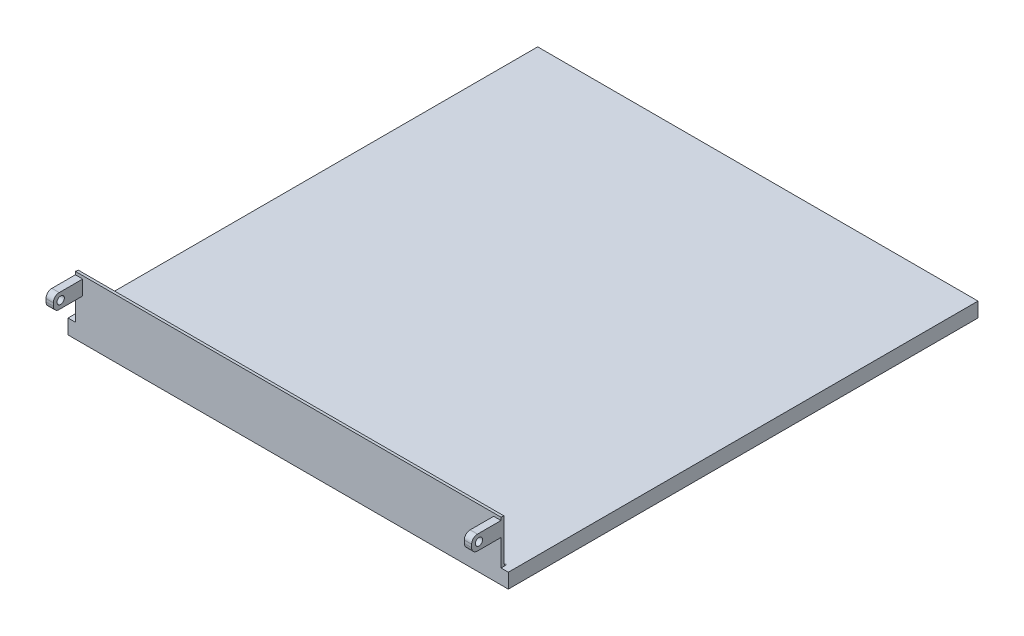
SolidWorks part; units mm, degrees
material "POLYURETHANE (11671)"
ref_plane "Front Plane" through (0, 0, 0) normal (0, 0, 1) x (1, 0, 0)
ref_plane "Top Plane" through (0, 0, 0) normal (0, 1, 0) x (1, 0, 0)
ref_plane "Right Plane" through (0, 0, 0) normal (1, 0, 0) x (0, 0, -1)
sketch "Sketch1" plane through (0, 0, 0) normal (0, 1, 0) x (1, 0, 0)
  line L1 (190.5, -203.2) -> (-190.5, -203.2)
  line L2 (190.5, -203.2) -> (190.5, 203.2)
  line L3 (190.5, 203.2) -> (-190.5, 203.2)
  line L4 (-190.5, -203.2) -> (-190.5, 203.2)
  line L5 (190.5, -203.2) -> (-190.5, 203.2) construction
  line L6 (190.5, 203.2) -> (-190.5, -203.2) construction
  point P0 (0, 0)
  dimension "D1" = 381
  dimension "D2" = 406.4
extrude "Boss-Extrude1" add sketch "Sketch1" against normal blind 12.7
sketch "Sketch2" plane through (0, -12.7, 0) normal (0, -1, 0) x (-1, 0, 0)
  line L0 (0, -203.2) -> (0, 203.2)
  line L1 (190.5, -203.2) -> (-190.5, -203.2) construction
  line L2 (-190.5, 203.2) -> (190.5, 203.2) construction
sketch "Sketch3" plane through (0, 0, 0) normal (1, 0, 0) x (0, 0, -1)
  line L0 (203.2, 0) -> (-203.2, 0)
sketch "Sketch5" plane through (0, 0, -203.2) normal (0, 0, -1) x (-1, 0, 0)
  line L0 (-190.5, 0) -> (0, -12.7)
  line L1 (-190.5, -12.7) -> (190.5, -12.7) construction
  line L2 (0, -12.7) -> (-190.5, -12.7)
  line L3 (-190.5, -12.7) -> (-190.5, 0)
  line L4 (0, -12.7) -> (190.5, -12.7)
  line L5 (190.5, -12.7) -> (190.5, 0)
  line L6 (190.5, 0) -> (0, -12.7)
  line M2 (-190.5, 0) -> (-190.5, -12.7)
  line M3 (-190.5, -12.7) -> (190.5, -12.7)
  line M4 (190.5, -12.7) -> (190.5, 0)
extrude "Cut-Extrude1" cut sketch "Sketch5" against normal blind 530.86 contours L6 M4 M3 | L0 M2 M3 region at (-127, -8.4667, -203.2) region at (127, -8.4667, -203.2)
sketch "Sketch6" plane through (0, 0, 0) normal (1, 0, 0) x (0, 0, -1)
  line L0 (-203.2, 0) -> (-203.2, 38.1)
  line L1 (-203.2, 0) -> (203.2, 0)
  spline S0 degree 3 poles (-203.2, 38.1) (-139.6712, 43.8544) (-4.5758, 44.1316) (127.0113, 22.2601) (203.2, 0) knots 0 0 0 0 0.446113 1 1 1 1
extrude "Boss-Extrude2" add sketch "Sketch6" along normal blind 190.5 and the other way blind 190.5
extrude "Cut-Extrude2" cut sketch "Sketch6<2>" against normal blind 185.42 and the other way blind 185.42
sketch "Sketch6<2>" plane through (0, 0, 0) normal (1, 0, 0) x (0, 0, -1) same geometry as "Sketch6"
sketch "Sketch9" plane through (0, 0, 0) normal (0, 0, 1) x (1, 0, 0)
  line L0 (-185.42, 0) -> (-185.42, 38.1)
  line L1 (-185.42, 38.1) -> (185.42, 38.1)
  line L2 (185.42, 38.1) -> (185.42, 0)
  line L3 (185.42, 0) -> (-185.42, 0)
extrude "Boss-Extrude3" add sketch "Sketch9" along normal blind 203.2
extrude "Cut-Extrude3" cut sketch "Sketch9<2>" along normal blind 200.66
sketch "Sketch9<2>" plane through (0, 0, 0) normal (0, 0, 1) x (1, 0, 0) same geometry as "Sketch9"
fillet "Fillet12" radius 2.54 1 edges at (0, 0, 200.66)
sketch "Sketch20" plane through (0, 0, 203.2) normal (0, 0, 1) x (1, 0, 0)
  line L0 (-190.5, 0) -> (190.5, 0)
  line L1 (-190.5, 0) -> (-190.5, -12.7)
  line L2 (190.5, 0) -> (190.5, -12.7)
  line L3 (-190.5, -12.7) -> (190.5, -12.7)
extrude "Boss-Extrude5" add sketch "Sketch20" against normal up to surface (406.4 mm away) up to face at (0, -2.54, -203.2)
sketch "Sketch21" plane through (0, 0, 0) normal (1, 0, 0) x (0, 0, -1)
  line L0 (-203.2, 38.1) -> (-203.2, 89.2755)
  line L1 (-203.2, 89.2755) -> (140.4963, 63.6877)
  line L2 (140.4963, 63.6877) -> (140.4963, 16.2471)
  spline S0 degree 2 poles (-203.2, 38.1) (-32.0596, 17.6919) (140.4963, 16.2471) knots 0 0 0 1 1 1
  spline S1 degree 3 poles (203.2, 0) (127.0113, 22.2601) (-4.5758, 44.1316) (-139.6712, 43.8544) (-203.2, 38.1) knots 0 0 0 0 0.553887 1 1 1 1 construction
extrude "Cut-Extrude10" cut sketch "Sketch21" against normal blind 259.334 and the other way blind 304.8
sketch "Sketch27" plane through (0, 0, 0) normal (1, 0, 0) x (0, 0, -1)
  line L5 (-203.2, 35.56) -> (-228.6, 35.56)
  line L6 (-203.2, 35.56) -> (-203.2, 22.86)
  line L7 (-228.6, 35.56) -> (-228.6, 22.86)
  line L8 (-203.2, 22.86) -> (-228.6, 22.86)
  line L9 (-203.2, 38.1) -> (-203.2, -12.7) construction
  circle A0 centre (-222.25, 29.21) radius 3.175
  dimension "D1" = 25.4
  dimension "D2" = 12.7
extrude "Boss-Extrude6" add sketch "Sketch27" along normal blind 184.15 and the other way blind 184.15
extrude "Cut-Extrude11" cut sketch "Sketch27<2>" against normal blind 177.8 and the other way blind 177.8
sketch "Sketch27<2>" plane through (0, 0, 0) normal (1, 0, 0) x (0, 0, -1) same geometry as "Sketch27"
fillet "Fillet14" radius 5.08 4 edges at (180.975, 35.56, 228.6) (180.975, 22.86, 228.6) (-180.975, 22.86, 228.6) (-180.975, 35.56, 228.6)
sketch "Sketch29" plane through (0, 0, 0) normal (0, 0, 1) x (1, 0, 0)
  line L1 (-190.5, 38.1) -> (-184.15, 38.1)
  line L2 (-190.5, 38.1) -> (-190.5, 0)
  line L3 (-190.5, 0) -> (-184.15, 0)
  line L4 (-184.15, 38.1) -> (-184.15, 0)
  line L5 (190.5, 38.1) -> (184.15, 38.1)
  line L6 (190.5, 38.1) -> (190.5, 0)
  line L7 (190.5, 0) -> (184.15, 0)
  line L8 (184.15, 38.1) -> (184.15, 0)
extrude "Cut-Extrude12" cut sketch "Sketch29" against normal through all and the other way through all
